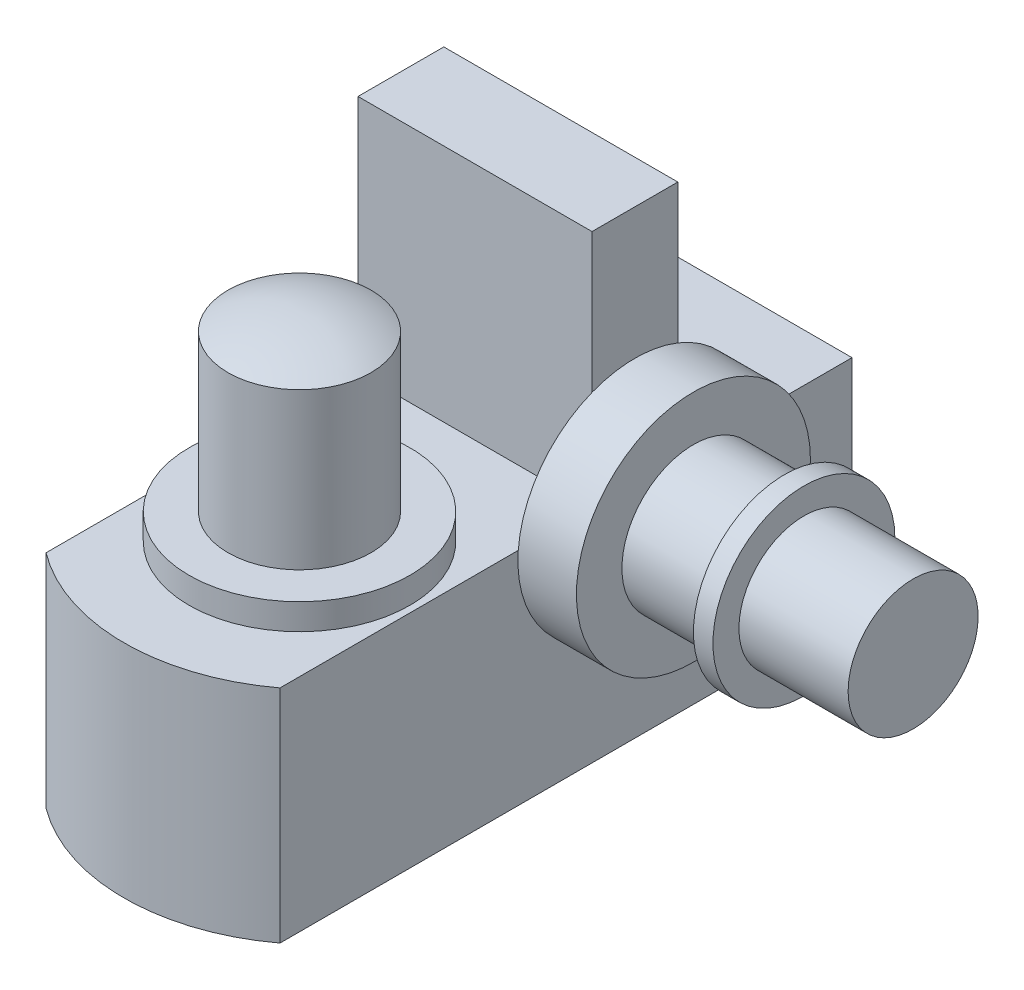
SolidWorks part; units mm, degrees
ref_plane "Front Plane" through (0, 0, 0) normal (0, 0, 1) x (1, 0, 0)
ref_plane "Top Plane" through (0, 0, 0) normal (0, 1, 0) x (1, 0, 0)
ref_plane "Right Plane" through (0, 0, 0) normal (1, 0, 0) x (0, 0, -1)
sketch "Sketch2" plane through (0, 0, 0) normal (0, 1, 0) x (1, 0, 0)
  line L0 (-45, 60) -> (-45, 160)
  line L1 (45, 60) -> (45, 160)
  line L2 (-45, 160) -> (45, 160)
  line L3 (45, -60) -> (-45, -60) construction
  line L4 (-45, -60) -> (-45, 60)
  line L5 (45, -60) -> (45, 60)
  line L6 (-2040.2273, -75) -> (99748.3732, -75) construction
  arc A1 (-45, -60) -> (45, -60) centre (0, 0) ccw
  arc A2 (-45, 60) -> (-45, -60) centre (0, 0) ccw construction
  arc A3 (45, 60) -> (-45, 60) centre (0, 0) ccw construction
  arc A4 (45, -60) -> (45, 60) centre (0, 0) ccw construction
  dimension "D2" = 90
  dimension "D1" = 15
  dimension "D3" = 220
extrude "Boss-Extrude1" add sketch "Sketch2" along normal mid plane 85
sketch "Sketch3" plane through (0, 42.5, 0) normal (0, 1, 0) x (1, 0, 0)
  line L0 (-1006.5186, -50) -> (48993.4814, -50) construction
  circle A0 centre (0, -7.5) radius 42.5
  dimension "D1" = 85
  dimension "D2" = 10
extrude "Boss-Extrude2" add sketch "Sketch3" along normal blind 10
sketch "Sketch4" plane through (0, 52.5, 0) normal (0, 1, 0) x (1, 0, 0)
  circle A0 centre (0, -7.5) radius 27.5
  circle A1 centre (0, -7.5) radius 42.5 construction
  dimension "D1" = 55
extrude "Boss-Extrude3" add sketch "Sketch4" along normal blind 60
sketch "Sketch5" plane through (0, 0, 0) normal (1, 0, 0) x (0, 0, -1)
  line L0 (-35, 112.5) -> (-7.5, 112.5)
  line L1 (20, 112.5) -> (-35, 112.5) construction
  line L2 (-7.5, 112.5) -> (-7.5, 119.1732)
  arc A0 (-7.5, 119.1732) -> (-35, 112.5) centre (-7.5, 59.1732) ccw
  arc A1 (-35, 112.5) -> (-7.5, 119.1732) centre (-7.5, 59.1732) ccw construction
  dimension "D1" = 120
revolve "Revolve1" add sketch "Sketch5" angle 360 about L2
sketch "Sketch6" plane through (0, 42.5, 0) normal (0, 1, 0) x (1, 0, 0)
  line L0 (45, -60) -> (45, 160) construction
  line L1 (-45, 93) -> (45, 93)
  line L2 (-45, 93) -> (-45, 60)
  line L3 (-45, 60) -> (45, 60)
  line L4 (45, 93) -> (45, 60)
  line L5 (-45, 93) -> (45, 60) construction
  line L6 (-45, 60) -> (45, 93) construction
  line L7 (-45, 160) -> (-45, -60) construction
  line L8 (-1000, 35) -> (49000, 35) construction
  circle A1 centre (0, -7.5) radius 42.5 construction
  point P0 (0, 76.5)
  dimension "D1" = 33
  dimension "D2" = 25
extrude "Boss-Extrude4" add sketch "Sketch6" along normal blind 92
ref_axis "Path of Light" through (0, 112.5, 7.5) along (0, -1, 0)
sketch "Sketch7" plane through (45, 0, 0) normal (1, 0, 0) x (0, 0, -1)
  line L0 (60, 134.5) -> (93, 134.5) construction
  circle A0 centre (76.5, 39.0521) radius 45
  point P2 (76.5, 134.5)
  point P3 (0, 0)
  dimension "D1" = 90
extrude "Boss-Extrude5" add sketch "Sketch7" along normal blind 22.5
sketch "Sketch9" plane through (67.5, 0, 0) normal (1, 0, 0) x (0, 0, -1)
  circle A0 centre (76.5, 39.0521) radius 27.5
  circle A1 centre (76.5, 39.0521) radius 45 construction
  dimension "D1" = 55
extrude "Boss-Extrude6" add sketch "Sketch9" along normal blind 35
sketch "Sketch10" plane through (102.5, 0, 0) normal (1, 0, 0) x (0, 0, -1)
  circle A0 centre (76.5, 39.0521) radius 35
  circle A1 centre (76.5, 39.0521) radius 27.5 construction
  dimension "D1" = 7.5
extrude "Boss-Extrude7" add sketch "Sketch10" along normal blind 7.5
sketch "Sketch11" plane through (110, 0, 0) normal (1, 0, 0) x (0, 0, -1)
  circle A0 centre (76.5, 39.0521) radius 25
  circle A1 centre (76.5, 39.0521) radius 35 construction
  dimension "D1" = 50
extrude "Boss-Extrude8" add sketch "Sketch11" along normal blind 42
